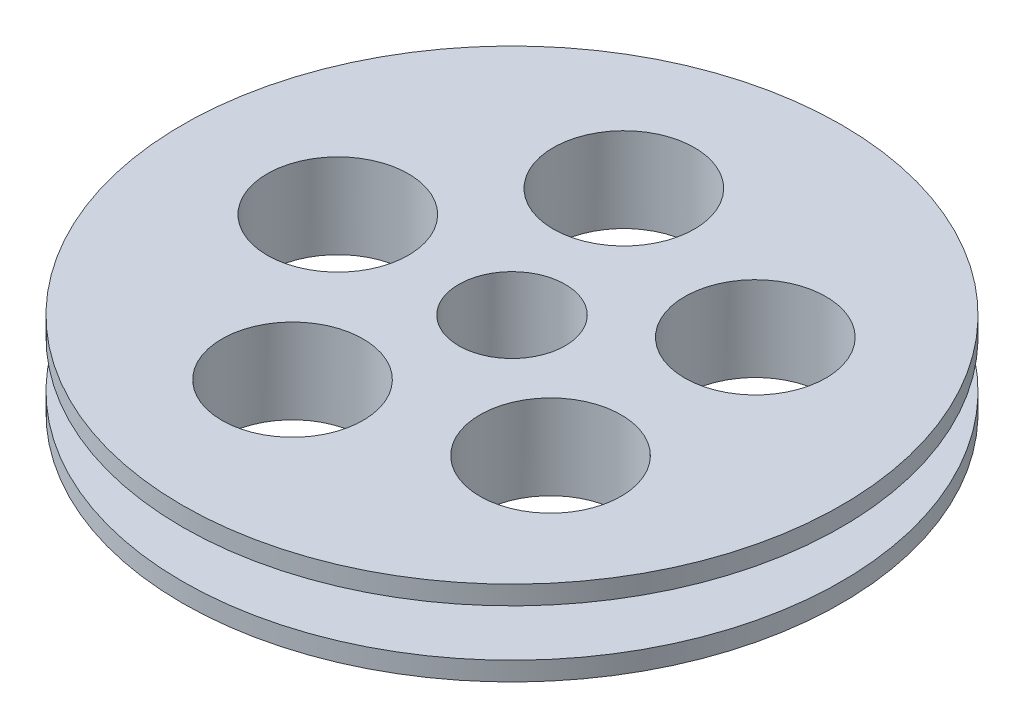
SolidWorks part; units mm, degrees
ref_plane "Front Plane" through (0, 0, 0) normal (0, 0, 1) x (1, 0, 0)
ref_plane "Top Plane" through (0, 0, 0) normal (0, 1, 0) x (1, 0, 0)
ref_plane "Right Plane" through (0, 0, 0) normal (1, 0, 0) x (0, 0, -1)
sketch "Sketch1" plane through (0, 0, 0) normal (1, 0, 0) x (0, 0, -1)
  line L0 (0, 2.5) -> (-5, 2.5) construction
  line L1 (0, 0) -> (30, 0)
  line L2 (0, 0) -> (0, -2)
  line L3 (0, -2) -> (30, -2)
  line L4 (30, 0) -> (30, -2)
  line L5 (0, 0) -> (22, 0)
  line L6 (0, 0) -> (0, 5)
  line L7 (0, 5) -> (22, 5)
  line L8 (22, 0) -> (22, 5)
  line L9 (0, 5) -> (30, 5)
  line L10 (0, 5) -> (0, 7)
  line L11 (0, 7) -> (30, 7)
  line L12 (30, 5) -> (30, 7)
  line L13 (-5, 2.5) -> (-5, 20.0021) construction
  dimension "D1" = 2
  dimension "D2" = 5
  dimension "D3" = 30
  dimension "D4" = 22
  dimension "D5" = 5
revolve "Revolve4" add sketch "Sketch1" angle 360 about L13 region at (0, 2.5, -11) region at (0, -1, -15) region at (0, 6, -15)
sketch "Sketch3" plane through (0, 7, 0) normal (0, 1, 0) x (1, 0, 0)
  circle A0 centre (0, -5) radius 5.6537
  circle A1 centre (0, -5) radius 5 construction
  circle A2 centre (-18.5, -5) radius 7.5
  circle A3 centre (-5.7168, 12.5945) radius 7.5
  circle A4 centre (14.9668, 5.874) radius 7.5
  circle A5 centre (14.9668, -15.874) radius 7.5
  circle A6 centre (-5.7168, -22.5945) radius 7.5
  point P17 (0, -5)
  dimension "D2" = 15
  dimension "D1" = 18.5
  dimension "D3" = 5
extrude "Cut-Extrude1" cut sketch "Sketch3" against normal blind 10
